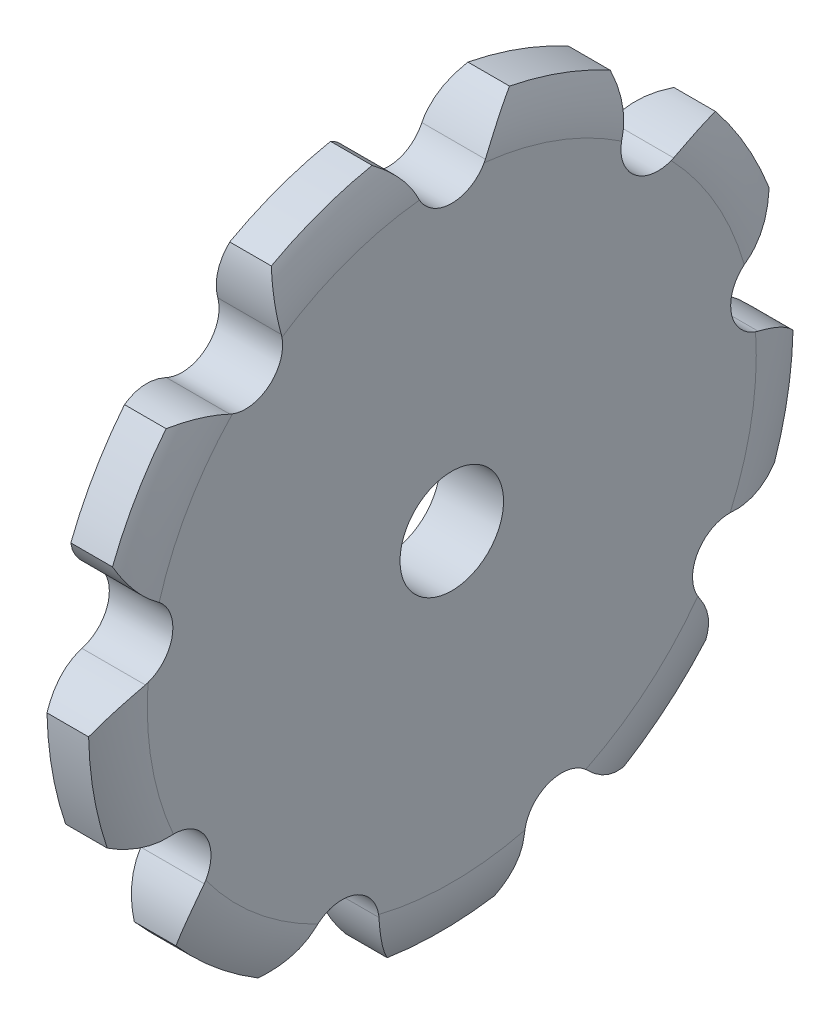
SolidWorks part; units mm, degrees
ref_plane "Plane1" through (0, 0, 0) normal (0, 0, 1) x (1, 0, 0)
ref_plane "Plane2" through (0, 0, 0) normal (0, 1, 0) x (1, 0, 0)
ref_plane "Plane3" through (0, 0, 0) normal (1, 0, 0) x (0, 0, -1)
sketch "Clipboard" plane through (0, 0, 0) normal (0, 1, 0) x (1, 0, 0)
  line L0 (0, 0) -> (25.0873, -3.9734)
  line L1 (-15, 0) -> (100, 0) construction
  line L2 (0, 0) -> (-0.8416, 0.9512)
  line L3 (0, 0) -> (-11.863, 4.5341)
  line L4 (0, 0) -> (3.0618, 0.4849)
  line L5 (0, 0) -> (-2.8109, -1.0484)
  line L6 (0, 0) -> (-6.1032, -4.1179)
  line L7 (-0.8416, 0.9512) -> (9.364, 2.7507)
  line L8 (-76.2, 38.1) -> (-75.2, 38.1)
  line L9 (-73.4361, 41.7391) -> (-72.4443, 41.8673)
  line L10 (-73.4741, 12.7512) -> (-59.5541, 12.7512)
  line L11 (-73.4741, 12.7512) -> (-59.1042, 12.5003)
  line L12 (-147.5013, -35.8225) -> (-147.5932, -35.8997)
  circle A0 centre (0, 0) radius 4.255
  circle A1 centre (0, 0) radius 25
  circle A2 centre (0, 0) radius 25
  dimension "Num_teeth" = 9
  dimension "Thickness" = 7.3625
sketch "BasProSke" plane through (0, 0, 0) normal (0, 1, 0) x (1, 0, 0)
  line L0 (-10, 0) -> (60, 0) construction
  line L1 (0, 0) -> (0, 35.279)
  line L2 (0, 0) -> (7.3625, 0)
  line L3 (7.3625, 0) -> (7.3625, 35.279)
  line L4 (6.0925, 40.8148) -> (1.27, 40.8148)
  arc A0 (0, 35.279) -> (1.27, 40.8148) centre (12.7, 35.279) cw
  arc A1 (7.3625, 35.279) -> (6.0925, 40.8148) centre (-5.3375, 35.279) ccw
  dimension "D1" = 12.7
  dimension "Thickness" = 7.3625
  dimension "Diameter" = 81.6296
revolve "Base-Revolve" add sketch "BasProSke" angle 360 about L0
sketch "TooCutSke" plane through (0, 0, 0) normal (1, 0, 0) x (0, 0, -1)
  line L0 (0, 37.1749) -> (3.8949, 35.3586) construction
  line L1 (0, 0) -> (0, 107) construction
  line L2 (0, 37.1749) -> (-10, 37.1749) construction
  line L3 (0, 37.1749) -> (-3.8949, 35.3586) construction
  arc A0 (3.8949, 35.3586) -> (7.9688, 40.0395) centre (14.0756, 30.6113) cw
  arc A1 (3.8949, 35.3586) -> (-3.8949, 35.3586) centre (0, 37.1749) cw
  arc A2 (-3.8949, 35.3586) -> (-7.9688, 40.0395) centre (-14.0756, 30.6113) ccw
  arc A3 (7.9688, 40.0395) -> (-7.9688, 40.0395) centre (0, 0) ccw
extrude "ToothCut" cut sketch "TooCutSke" along normal through all
pattern_circular "TeethCuts" count 9 every 40 about axis through (-10, 0, 0) along (1, 0, 0) of "ToothCut"
sketch "HubNeaOneSke" plane through (0, 0, 0) normal (-1, 0, 0) x (0, 0, 1)
  circle A0 centre (0, 0) radius 25
  dimension "Diameter" = 50
extrude "HubNearOne" [suppressed] add sketch "HubNeaOneSke" along normal blind 3.0005
fillet "HubNearOneFillet" [suppressed] radius 1
sketch "HubNeaBotSke" plane through (0, 0, 0) normal (-1, 0, 0) x (0, 0, 1)
  circle A0 centre (0, 0) radius 25
  dimension "Diameter" = 50
extrude "HubNearBoth" [suppressed] add sketch "HubNeaBotSke" along normal blind 1.5003
fillet "HubNearBothFillet" [suppressed] radius 1
ref_plane "FarPln" through (7.3625, 0, 0) normal (1, 0, 0) x (0, 0, -1)
sketch "HubFarSke" plane through (7.3625, 0, 0) normal (1, 0, 0) x (0, 0, -1)
  circle A0 centre (0, 0) radius 25
  dimension "Diameter" = 50
extrude "HubFar" [suppressed] add sketch "HubFarSke" along normal blind 1.5003
fillet "HubFarFillet" [suppressed] radius 1
sketch "BorSke" plane through (0, 0, 0) normal (1, 0, 0) x (0, 0, -1)
  circle A0 centre (0, 0) radius 6
  dimension "Diameter" = 12
extrude "Bore" cut sketch "BorSke" along normal mid plane 20.726
sketch "KeySke" plane through (0, 0, 0) normal (1, 0, 0) x (0, 0, -1)
  line L0 (-1, 0) -> (-1, 7)
  line L1 (-1, 7) -> (1, 7)
  line L2 (1, 7) -> (1, 0)
  line L3 (0, 0) -> (0, 34) construction
  line L4 (-1, 0) -> (1, 0)
  dimension "Width" = 2
extrude "Keyway" [suppressed] cut sketch "KeySke" along normal mid plane 20.726
pattern_circular "Keyway2" [suppressed] count 2 every 90 about axis through (-10, 0, 0) along (1, 0, 0) reverse direction yes
equation "' \"Pitch@Clipboard\" = 25.4"
equation "' \"Num_teeth@Clipboard\" = 9"
equation "' \"Hub_dia@Clipboard\" = 50"
equation "' \"Overall_len@Clipboard\" = 3"
equation "' \"Diameter@BorSke\" = 12"
equation "' \"T_dim@Clipboard\" = 1"
equation "' \"Width@KeySke\" = 2"
equation "' \"Dr@Clipboard\" = 8.51"
equation "' \"Face_width@Clipboard\" = 7.3625"
equation "' \"Side_radius@Clipboard\" = 12.7"
equation "' \"Side_relief@Clipboard\" = 1.27"
equation "' \"Show_teeth@Clipboard\" = 9"
equation "' \"Fillet_rad@Clipboard\" = 1"
equation "' \"Plate_wid@Clipboard\" = 11.8"
equation "'  \"Cut@Clipboard\" = 1"
equation "'  \"GapAngle@Clipboard\" = 140"
equation "'  \"GapFactor@Clipboard\" = 0.12"
equation "' \"Num_teeth@Clipboard\" = int( \"Num_teeth@Clipboard\" )"
equation "\"Num_teeth@Clipboard\" = ((sgn( \"Num_teeth@Clipboard\" - 5.0)+1)*( \"Num_teeth@Clipboard\" - 5.0))/2 +5.0"
equation "\"Num_teeth@Clipboard\" = ((sgn( \"Num_teeth@Clipboard\" - 200.0)-1)*( \"Num_teeth@Clipboard\" - 200.0))/-2 +200.0"
equation "\"MHD@Clipboard\" = \"Pitch@Clipboard\" * (1.0 / tan(3.14159265 / \"Num_teeth@Clipboard\" )) - 1.05 * \"Plate_wid@Clipboard\" - 2.0 * \"Fillet_rad@Clipboard\" - 1.0"
equation "\"Thickness@Clipboard\"  = \"Face_width@Clipboard\" + (\"Num_strands@Clipboard\" - 1) * \"Transv_pitch@Clipboard\""
equation "\"OAL@Clipboard\" = \"Thickness@Clipboard\" + 2 * \"Fillet_rad@Clipboard\" + 1"
equation "\"MHD@Clipboard\" = ((sgn( \"MHD@Clipboard\" - \"Hub_dia@Clipboard\" )-1)*( \"MHD@Clipboard\" - \"Hub_dia@Clipboard\" ))/-2+ \"Hub_dia@Clipboard\""
equation "\"OAL@Clipboard\" = ((sgn( \"OAL@Clipboard\" - \"Overall_len@Clipboard\" )+1)*( \"OAL@Clipboard\" - \"Overall_len@Clipboard\" ))/2 + \"Overall_len@Clipboard\" + 0.0005"
equation "\"Num_teeth@TeethCuts\" = int( \"Show_teeth@Clipboard\" ) + 1"
equation "\"Num_teeth@TeethCuts\" = ((sgn( \"Num_teeth@TeethCuts\" - \"Num_teeth@Clipboard\" )-1)*( \"Num_teeth@TeethCuts\" - \"Num_teeth@Clipboard\" ))/-2+ \"Num_teeth@Clipboard\""
equation "\"Num_teeth@TeethCuts\" = ((sgn( \"Num_teeth@TeethCuts\" - 2.0)+1)*( \"Num_teeth@TeethCuts\" - 2.0))/2 +2.0"
equation "\"Angle@TeethCuts\" = 360.0 / \"Num_teeth@Clipboard\""
equation "\"Num_teeth@TeethCuts\" = \"Num_teeth@TeethCuts\" * \"Cut@Clipboard\""
equation "\"Angle@TeethCuts\" = \"Angle@TeethCuts\" / \"Cut@Clipboard\""
equation "\"Seat_radius@TooCutSke\" = ( \"Pitch@Clipboard\" / 2.0) / sin(3.14159265 / \"Num_teeth@Clipboard\" ) - \"Dr@Clipboard\" / 2.0 + \"Dr@Clipboard\" * 0.505"
equation "\"R1@TooCutSke\"  = \"Dr@Clipboard\" * 0.505"
equation "\"X@TooCutSke\" = \"GapAngle@Clipboard\" - (90.0 / \"Num_teeth@Clipboard\")"
equation "\"R2@TooCutSke\" = \"GapFactor@Clipboard\"  * \"Dr@Clipboard\" * ( \"Num_teeth@Clipboard\" + 2.0)"
equation "' \"R2@TooCutSke\" = 0.008 * \"Dr@Clipboard\" * ( \"Num_teeth@Clipboard\" * \"Num_teeth@Clipboard\" + 180)"
equation "\"Overcut@TooCutSke\" = 0.01 + 0.625 / 2 * \"Pitch@Clipboard\" - 0.5 * \"Dr@Clipboard\"  +  \"Pitch@Clipboard\" / 2.0 / sin(3.14159265 / \"Num_teeth@Clipboard\" )"
equation "\"Diameter@BasProSke\" = 2.0 * ( 0.625 / 2 * \"Pitch@Clipboard\" - 0.5 * \"Dr@Clipboard\"  +  \"Pitch@Clipboard\" / 2.0 / sin(3.14159265 / \"Num_teeth@Clipboard\" ))"
equation "\"Thickness@BasProSke\"  = \"Thickness@Clipboard\""
equation "\"G1@BasProSke\" =  \"Side_relief@Clipboard\""
equation "\"G2@BasProSke\" =  \"Side_relief@Clipboard\""
equation "\"D1@BasProSke\" =  \"Side_radius@Clipboard\""
equation "\"Diameter@HubNeaOneSke\" = \"MHD@Clipboard\""
equation "\"Length@HubNearOne\" = \"OAL@Clipboard\" - \"Thickness@BasProSke\""
equation "\"Diameter@HubNeaBotSke\" = \"MHD@Clipboard\""
equation "\"Length@HubNearBoth\" = ( \"OAL@Clipboard\" - \"Thickness@BasProSke\" ) / 2.0"
equation "\"D1@HubNearOneFillet\" = \"Fillet_rad@Clipboard\""
equation "\"D1@HubNearBothFillet\" = \"Fillet_rad@Clipboard\""
equation "\"Thickness@FarPln\" = \"Thickness@BasProSke\""
equation "\"Diameter@HubFarSke\" = \"MHD@Clipboard\""
equation "\"Length@HubFar\" = ( \"OAL@Clipboard\" - \"Thickness@BasProSke\" ) / 2.0"
equation "\"D1@HubFarFillet\" = \"Fillet_rad@Clipboard\""
equation "\"D1@Bore\" = \"OAL@Clipboard\" * 2.0"
equation "\"D1@Keyway\" = \"OAL@Clipboard\" * 2.0"
equation "\"Offset@KeySke\" = \"T_dim@Clipboard\" + \"Diameter@BorSke\" / 2.0"
